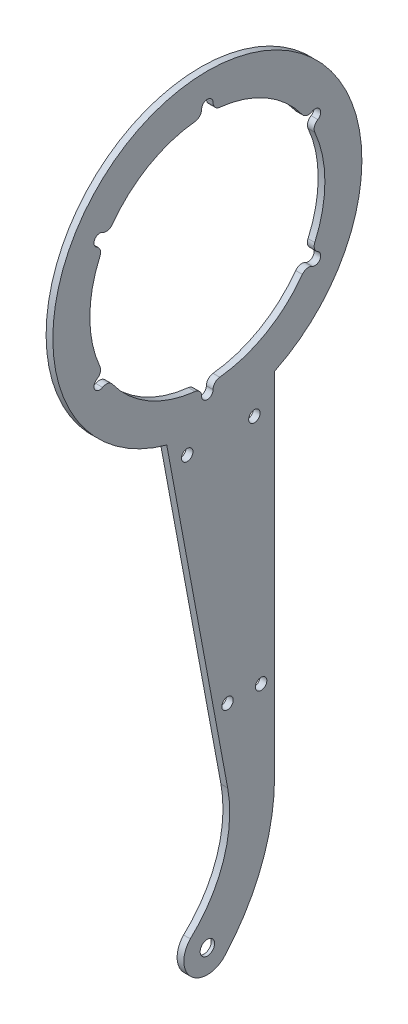
SolidWorks part; units mm, degrees
ref_plane "前视基准面" through (0, 0, 0) normal (0, 0, 1) x (1, 0, 0)
ref_plane "上视基准面" through (0, 0, 0) normal (0, 1, 0) x (1, 0, 0)
ref_plane "右视基准面" through (0, 0, 0) normal (1, 0, 0) x (0, 0, -1)
sketch "草图1" plane through (0, 0, 0) normal (1, 0, 0) x (0, 0, -1)
  line L10 (-12.0867, -44.3837) -> (6.0415, -141.8339)
  line L13 (20, -146.0922) -> (20, -41.4246)
  arc A21 (20, -41.4246) -> (-12.0867, -44.3837) centre (0, 0) ccw
  arc A22 (20, -146.0922) -> (5.2059, -184.6796) centre (-37.7208, -146.0922) cw
  arc A23 (5.2059, -184.6796) -> (-5.0762, -175.1801) centre (0, -180) cw
  circle A24 centre (0, -180) radius 2.15
  arc A25 (6.0415, -141.8339) -> (-5.0762, -175.1801) centre (-29.6255, -148.4689) cw
  circle A26 centre (-6, -50) radius 1.7
  circle A27 centre (14, -50) radius 1.7
  circle A28 centre (6, -120) radius 1.7
  circle A29 centre (16, -120) radius 1.7
  arc A30 (1.7, -37) -> (3.6883, -34.7898) centre (3.9226, -37) cw
  arc A33 (1.7, -37) -> (-1.7, -37) centre (0, -37) cw
  arc A34 (-1.7, -37) -> (-3.6883, -34.7898) centre (-3.9226, -37) ccw
  arc A35 (-32.8929, -17.0278) -> (-31.973, -14.2008) centre (-34.0042, -15.1029) ccw
  arc A36 (-31.1929, -19.9722) -> (-32.8929, -17.0278) centre (-32.0429, -18.5) cw
  arc A37 (-31.1929, -19.9722) -> (-28.2847, -20.589) centre (-30.0817, -21.8971) cw
  arc A38 (-31.1929, 19.9722) -> (-28.2847, 20.589) centre (-30.0817, 21.8971) ccw
  arc A39 (-32.8929, 17.0278) -> (-31.1929, 19.9722) centre (-32.0429, 18.5) cw
  arc A40 (-32.8929, 17.0278) -> (-31.973, 14.2008) centre (-34.0042, 15.1029) cw
  arc A41 (1.7, 37) -> (3.6883, 34.7898) centre (3.9226, 37) ccw
  arc A42 (-1.7, 37) -> (1.7, 37) centre (0, 37) cw
  arc A43 (-1.7, 37) -> (-3.6883, 34.7898) centre (-3.9226, 37) cw
  arc A44 (32.8929, 17.0278) -> (31.973, 14.2008) centre (34.0042, 15.1029) ccw
  arc A45 (31.1929, 19.9722) -> (32.8929, 17.0278) centre (32.0429, 18.5) cw
  arc A46 (31.1929, 19.9722) -> (28.2847, 20.589) centre (30.0817, 21.8971) cw
  arc A47 (31.1929, -19.9722) -> (28.2847, -20.589) centre (30.0817, -21.8971) ccw
  arc A48 (32.8929, -17.0278) -> (31.1929, -19.9722) centre (32.0429, -18.5) cw
  arc A49 (32.8929, -17.0278) -> (31.973, -14.2008) centre (34.0042, -15.1029) cw
  arc A50 (-31.973, 14.2008) -> (-31.973, -14.2008) centre (0, 0) ccw
  arc A51 (-28.2847, -20.589) -> (-3.6883, -34.7898) centre (0, 0) ccw
  arc A52 (28.2847, -20.589) -> (3.6883, -34.7898) centre (0, 0) cw
  arc A53 (31.973, 14.2008) -> (31.973, -14.2008) centre (0, 0) cw
  arc A54 (28.2847, 20.589) -> (3.6883, 34.7898) centre (0, 0) ccw
  arc A55 (-3.6883, 34.7898) -> (-28.2847, 20.589) centre (0, 0) ccw
  point P79 (0, 0)
extrude "凸台-拉伸3" add sketch "草图1" along normal blind 2
sketch "草图2" plane through (0, 0, 0) normal (-1, 0, 0) x (0, 0, 1)
  circle A0 centre (0, -180) radius 5
extrude "切除-拉伸1" cut sketch "草图2" against normal blind 1
